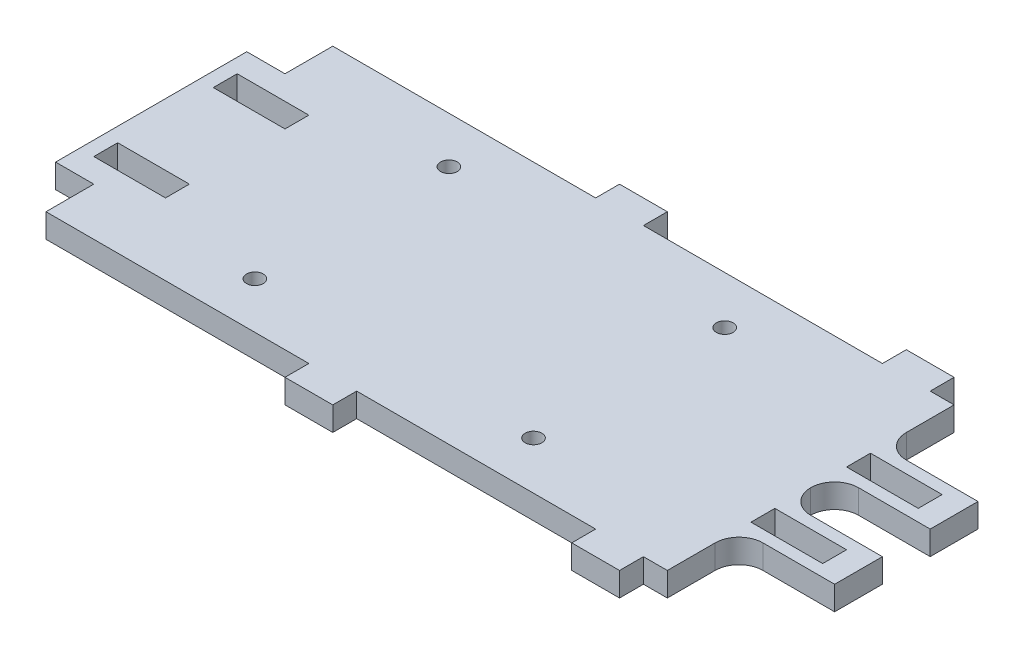
SolidWorks part; units mm, degrees
ref_plane "Front Plane" through (0, 0, 0) normal (0, 0, 1) x (1, 0, 0)
ref_plane "Top Plane" through (0, 0, 0) normal (0, 1, 0) x (1, 0, 0)
ref_plane "Right Plane" through (0, 0, 0) normal (1, 0, 0) x (0, 0, -1)
sketch "Sketch1" plane through (0, 0, 0) normal (0, 1, 0) x (1, 0, 0)
  line L0 (65, 15) -> (65, 30)
  line L1 (-65, -30) -> (-10, -30)
  line L2 (-65, -30) -> (-65, -20)
  line L3 (-65, 30) -> (-10, 30)
  line L4 (65, -30) -> (65, -15)
  line L5 (60, 30) -> (65, 30)
  line L8 (-10, 30) -> (-10, 35)
  line L9 (-10, 35) -> (0, 35)
  line L10 (0, 30) -> (0, 35)
  line L16 (-10, -30) -> (-10, -35)
  line L17 (-10, -35) -> (0, -35)
  line L18 (0, -30) -> (0, -35)
  line L27 (65, 15) -> (85, 15)
  line L28 (65, 12.5) -> (65, 7.5)
  line L29 (65, 5) -> (85, 5)
  line L30 (85, 15) -> (85, 5)
  line L31 (65, -5) -> (85, -5)
  line L32 (65, -7.5) -> (65, -12.5)
  line L33 (65, -15) -> (85, -15)
  line L34 (85, -5) -> (85, -15)
  line L35 (65, 7.5) -> (80, 7.5)
  line L36 (65, 7.5) -> (65, 12.5)
  line L37 (65, 12.5) -> (80, 12.5)
  line L38 (80, 7.5) -> (80, 12.5)
  line L39 (65, -12.5) -> (80, -12.5)
  line L40 (65, -12.5) -> (65, -7.5)
  line L41 (65, -7.5) -> (80, -7.5)
  line L42 (80, -12.5) -> (80, -7.5)
  line L43 (65, 7.5) -> (65, 12.5)
  line L44 (65, -5) -> (65, 5)
  line L45 (0, 30) -> (50, 30)
  line L46 (0, -30) -> (50, -30)
  line L47 (65, -12.5) -> (65, -7.5)
  line L48 (60, -30) -> (60, -35)
  line L49 (60, -35) -> (50, -35)
  line L50 (50, -30) -> (50, -35)
  line L52 (60, 30) -> (60, 35)
  line L53 (60, 35) -> (50, 35)
  line L54 (50, 30) -> (50, 35)
  line L55 (60, -30) -> (65, -30)
  line L56 (-50.05, 30) -> (-50.05, -30) construction
  line L57 (-72.9924, -5) -> (-72.9924, -20)
  line L58 (-65, 20) -> (-72.9924, 20)
  line L60 (-65, -20) -> (-72.9924, -20)
  line L61 (-72.9924, 20) -> (-72.9924, 5)
  line L62 (-55, 15) -> (-70, 15)
  line L63 (-55, 15) -> (-55, 10)
  line L64 (-55, 10) -> (-70, 10)
  line L65 (-70, 15) -> (-70, 10)
  line L66 (-55, -15) -> (-70, -15)
  line L67 (-55, -15) -> (-55, -10)
  line L68 (-55, -10) -> (-70, -10)
  line L69 (-70, -15) -> (-70, -10)
  line L70 (-65, 20) -> (-65, 30)
  line L75 (-72.9924, 5) -> (-72.9924, -5)
  circle A0 centre (27, 20) radius 1.75
  circle A1 centre (27, -20) radius 1.75
  circle A2 centre (-31, 20.3) radius 1.75
  circle A4 centre (-31, -20.3) radius 1.75
  point P0 (0, 0)
  dimension "D28" = 3.5
  dimension "D29" = 3.5
  dimension "D31" = 9.7
  dimension "D33" = 3.5
  dimension "D34" = 3.5
  dimension "D1" = 130
  dimension "D2" = 60
  dimension "D3" = 10
  dimension "D4" = 10
  dimension "D5" = 5
  dimension "D6" = 10
  dimension "D7" = 5
  dimension "D8" = 5
  dimension "D9" = 75
  dimension "D10" = 5
  dimension "D11" = 38
  dimension "D12" = 10
  dimension "D13" = 75
  dimension "D14" = 15
  dimension "D15" = 15
  dimension "D16" = 10
  dimension "D17" = 10
  dimension "D18" = 2.5
  dimension "D19" = 2.5
  dimension "D20" = 20
  dimension "D21" = 20
  dimension "D22" = 2.5
  dimension "D23" = 2.5
  dimension "D24" = 5
  dimension "D25" = 10
  dimension "D26" = 5
  dimension "D27" = 40
  dimension "D30" = 40.6
  dimension "D32" = 9.7
  dimension "D35" = 19.05
  dimension "D36" = 14.95
  dimension "D37" = 60
  dimension "D38" = 5
  dimension "D39" = 20
  dimension "D40" = 15
  dimension "D41" = 15
  dimension "D42" = 15
  dimension "D44" = 0
  dimension "D45" = 10
  dimension "D46" = 10
extrude "Boss-Extrude1" add sketch "Sketch1" along normal blind 5 contours L48 L55 L4 L33 L34 L31 L44 L29 L30 L27 L0 L5 L52 L53 L54 L45 L10 L9 L8 L3 L2 L1 L16 L17 L18 L46 L50 L49 A1 A0 L38 L35 L28 L37 L42 L39 L32 L41 | L1 L16 L17 L18 L46 L50 L49 L48 L55 L4 L33 L34 L31 L44 L29 L30 L27 L0 L5 L52 L53 L54 L45 L10 L9 L8 L3 L70 L58 L61 L75 L57 L60 L2 | L63 L62 L65 L64 | L67 L66 L69 L68 | A2 | A4 | A0 | L36 L35 L38 L37 | L40 L39 L42 L41 | A1 region at (1.3744, 0, 0)
fillet "Fillet1" radius 5 4 edges at (65, 2.5, 15) (65, 2.5, 5) (65, 2.5, -5) (65, 2.5, -15)
